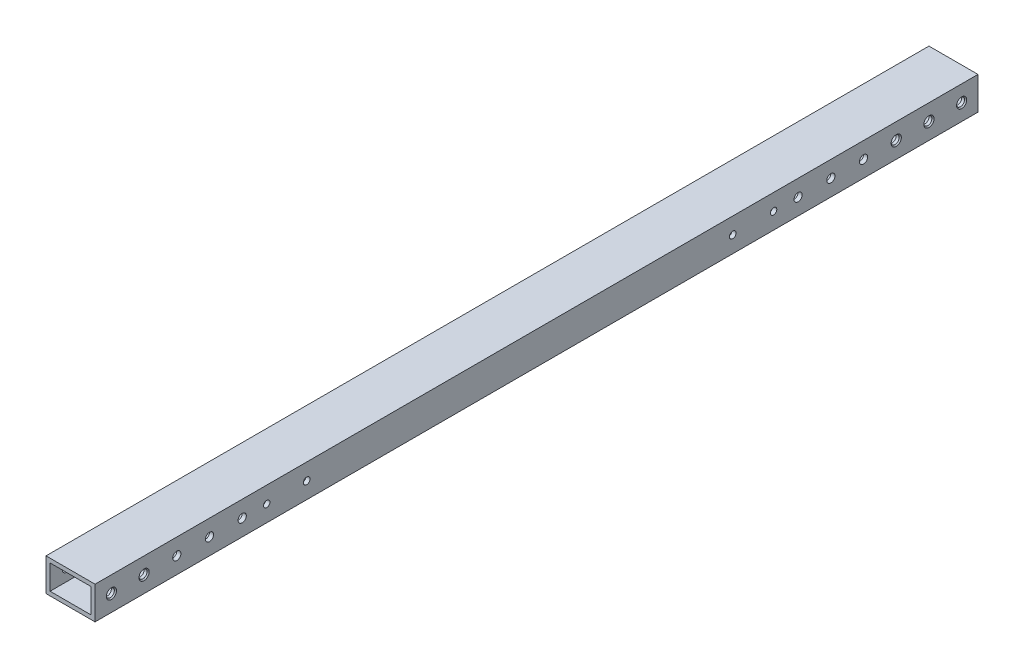
SolidWorks part; units mm, degrees
ref_plane "Front Plane" through (0, 0, 0) normal (0, 0, 1) x (1, 0, 0)
ref_plane "Top Plane" through (0, 0, 0) normal (0, 1, 0) x (1, 0, 0)
ref_plane "Right Plane" through (0, 0, 0) normal (1, 0, 0) x (0, 0, -1)
sketch "Sketch1" plane through (0, 0, 0) normal (0, 0, 1) x (1, 0, 0)
  line L0 (-15.875, 9.525) -> (15.875, 9.525)
  line L2 (-19.05, 12.7) -> (19.05, 12.7)
  line L3 (-19.05, 12.7) -> (-19.05, -12.7)
  line L4 (-19.05, -12.7) -> (19.05, -12.7)
  line L5 (19.05, 12.7) -> (19.05, -12.7)
  line L10 (15.875, 9.525) -> (15.875, -9.525)
  line L11 (-15.875, -9.525) -> (15.875, -9.525)
  line L12 (-15.875, 9.525) -> (-15.875, -9.525)
  point P12 (0, 12.7)
  point P14 (19.05, 0)
  dimension "Wall Thickness" = 3.175
  dimension "Outside Width" = 38.1
  dimension "Outside Height" = 25.4
  dimension "Inside Height" = 19.05
  dimension "Inside Width" = 31.75
sketch "Sketch2" plane through (0, 0, 0) normal (1, 0, 0) x (0, 0, -1)
  line L0 (342.9, 0) -> (-342.9, 0)
  point P4 (0, 0)
  point P7 (-342.9, 0)
  point P10 (342.9, 0)
  dimension "Length" = 685.8
sketch "Sketch3" plane through (0, 0, 0) normal (0, 0, 1) x (1, 0, 0)
  line L21 (19.05, 12.7) -> (-19.05, 12.7)
  line L22 (19.05, -12.7) -> (19.05, 12.7)
  line L23 (-19.05, -12.7) -> (19.05, -12.7)
  line L24 (-19.05, 12.7) -> (-19.05, -12.7)
  line L25 (19.05, 12.7) -> (-19.05, 12.7)
  line L26 (19.05, -12.7) -> (19.05, 12.7)
  line L27 (-19.05, -12.7) -> (19.05, -12.7)
  line L28 (-19.05, 12.7) -> (-19.05, -12.7)
  line L29 (15.875, 9.525) -> (-15.875, 9.525)
  line L30 (15.875, -9.525) -> (15.875, 9.525)
  line L31 (-15.875, -9.525) -> (15.875, -9.525)
  line L32 (-15.875, 9.525) -> (-15.875, -9.525)
  line L33 (15.875, 9.525) -> (-15.875, 9.525)
  line L34 (15.875, -9.525) -> (15.875, 9.525)
  line L35 (-15.875, -9.525) -> (15.875, -9.525)
  line L36 (-15.875, 9.525) -> (-15.875, -9.525)
  dimension "D1" = 0
  dimension "D2" = 0
extrude "Boss-Extrude1" add sketch "Sketch3" along normal up to vertex (342.9 mm away) and the other way up to vertex (342.9 mm away) up to point (0, 0, 342.9) other way up to point (0, 0, -342.9)
sketch "Drawing Reference" plane through (0, 0, 0) normal (1, 0, 0) x (0, 0, -1)
  line L0 (-342.9, 0) -> (342.9, 0) construction
  line L1 (0, -12.7) -> (0, 12.7) construction
  line L2 (-342.9, -12.7) -> (342.9, -12.7) construction
  line L5 (-342.9, 12.7) -> (342.9, 12.7) construction
  point P7 (-315.468, 0)
  point P8 (315.468, 0)
  dimension "D1" = 27.432
sketch "Sketch4" plane through (-19.05, 0, 0) normal (-1, 0, 0) x (0, 0, 1)
  line L0 (-342.9, 0) -> (-330.2, 0)
  line L1 (-342.9, 12.7) -> (-342.9, -12.7) construction
  line L2 (-330.2, 0) -> (-304.8, 0)
  line L3 (-304.8, 0) -> (-279.4, 0)
  line L4 (-279.4, 0) -> (-254, 0)
  line L5 (-254, 0) -> (-228.6, 0)
  line L6 (-228.6, 0) -> (-203.2, 0)
  line L7 (342.9, 0) -> (330.2, 0)
  line L8 (342.9, 12.7) -> (342.9, -12.7) construction
  line L9 (330.2, 0) -> (304.8, 0)
  line L10 (304.8, 0) -> (279.4, 0)
  line L11 (279.4, 0) -> (254, 0)
  line L12 (254, 0) -> (228.6, 0)
  line L13 (-203.2, 0) -> (-184.15, 0)
  line L14 (-203.2, 0) -> (-152.4, 0) construction
  line L15 (228.6, 0) -> (209.55, 0)
  line L16 (228.6, 0) -> (178.5118, 0) construction
hole_wizard "1/4 (0.25) Diameter Hole2" positions "Sketch7" profile "Sketch8" hole size "1/4" standard "ANSI Inch" end condition through all
sketch "Sketch7" plane through (-19.05, 0, 0) normal (-1, 0, 0) x (0, 0, 1)
  point P0 (-330.2, 0)
  point P3 (-304.8, 0)
  point P7 (330.2, 0)
  point P11 (-279.4, 0)
  point P14 (304.8, 0)
sketch "Sketch8" plane through (-19.05, 0, -330.2) normal (0, 1, 0) x (0, 0, 1)
  line L0 (0, 0) -> (0, 38.1)
  line L1 (0, 38.1) -> (3.9624, 38.1)
  line L2 (3.175, 37.1942) -> (3.175, 0)
  line L5 (3.175, 0) -> (0, 0)
  line L7 (3.9624, 38.1) -> (3.175, 37.1942)
  line L8 (-3.9624, 38.1) -> (-3.175, 37.1942) construction
  line L11 (0, -6.35) -> (0, 107.95) construction
  dimension "Thru Hole Dia." = 6.35
  dimension "Thru Hole Depth" = 38.1
  dimension "Far C'Sink Dia." = 7.9248
  dimension "Far C'Sink Angle" = 82
hole_wizard "1/4 (0.25) Diameter Hole3" positions "Sketch9" profile "Sketch10" hole size "1/4" standard "ANSI Inch" end condition through all
sketch "Sketch9" plane through (19.05, 0, 0) normal (1, 0, 0) x (0, 0, -1)
  point P0 (-279.4, 0)
  point P3 (-254, 0)
  point P6 (-228.6, 0)
  point P9 (254, 0)
  point P12 (228.6, 0)
  point P15 (203.2, 0)
sketch "Sketch10" plane through (19.05, 0, 279.4) normal (0, 1, 0) x (0, 0, -1)
  line L0 (0, 0) -> (0, 38.1)
  line L1 (0, 38.1) -> (3.175, 38.1)
  line L2 (3.175, 38.1) -> (3.175, 0)
  line L5 (3.175, 0) -> (0, 0)
  line L11 (0, -6.35) -> (0, 107.95) construction
  dimension "Thru Hole Dia." = 6.35
  dimension "Thru Hole Depth" = 38.1
hole_wizard "13/64 (0.20313) Diameter Hole1" positions "Sketch11" profile "Sketch12" hole size "13/64" standard "ANSI Inch" end condition through all
sketch "Sketch11" plane through (19.05, 0, 0) normal (1, 0, 0) x (0, 0, -1)
  point P0 (152.4, 0)
  point P3 (-178.5118, 0)
sketch "Sketch12" plane through (19.05, 0, -152.4) normal (0, 1, 0) x (0, 0, -1)
  line L0 (0, 0) -> (0, 38.1)
  line L1 (0, 38.1) -> (2.5798, 38.1)
  line L2 (2.5798, 38.1) -> (2.5798, 0)
  line L5 (2.5798, 0) -> (0, 0)
  line L11 (0, -6.35) -> (0, 107.95) construction
  dimension "Thru Hole Dia." = 5.1595
  dimension "Thru Hole Depth" = 38.1
hole_wizard "#10 (0.1935) Diameter Hole1" positions "Sketch13" profile "Sketch14" hole size "#10" standard "ANSI Inch" end condition through all
sketch "Sketch13" plane through (-19.05, 0, 0) normal (-1, 0, 0) x (0, 0, 1)
  point P0 (-184.15, 0)
  point P3 (209.55, 0)
sketch "Sketch14" plane through (-19.05, 0, -184.15) normal (0, 1, 0) x (0, 0, 1)
  line L0 (0, 0) -> (0, 38.1)
  line L1 (0, 38.1) -> (2.4574, 38.1)
  line L2 (2.4574, 38.1) -> (2.4574, 0)
  line L5 (2.4574, 0) -> (0, 0)
  line L11 (0, -6.35) -> (0, 107.95) construction
  dimension "Thru Hole Dia." = 4.9149
  dimension "Thru Hole Depth" = 38.1
equation "\"D1@Drawing Reference\"=\"Outside Width@Sketch1\" * 0.72"
